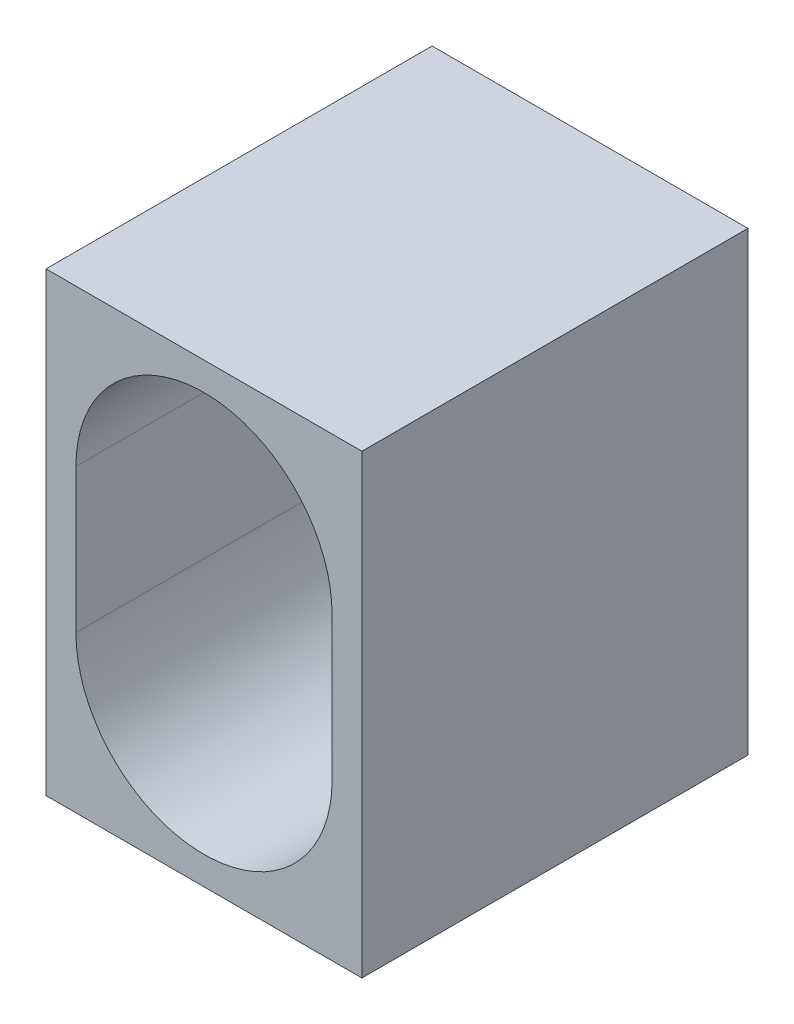
SolidWorks part; units mm, degrees
ref_plane "Front Plane" through (0, 0, 0) normal (0, 0, 1) x (1, 0, 0)
ref_plane "Top Plane" through (0, 0, 0) normal (0, 1, 0) x (1, 0, 0)
ref_plane "Right Plane" through (0, 0, 0) normal (1, 0, 0) x (0, 0, -1)
sketch "Sketch4" plane through (0, 0, 0) normal (0, 0, 1) x (1, 0, 0)
  line L1 (-30.2849, 20.5607) -> (14.7151, 20.5607)
  line L2 (-30.2849, 20.5607) -> (-30.2849, -44.4393)
  line L3 (-30.2849, -44.4393) -> (14.7151, -44.4393)
  line L4 (14.7151, 20.5607) -> (14.7151, -44.4393)
  dimension "D1" = 45
  dimension "D2" = 65
extrude "Boss-Extrude2" add sketch "Sketch4" along normal blind 55
sketch "Sketch5" plane through (0, 0, 55) normal (0, 0, 1) x (1, 0, 0)
  line L0 (-7.7849, -22.1893) -> (-7.7849, -1.6893) construction
  line L1 (-21.0349, -22.1893) -> (-21.0349, -1.6893) construction
  line L2 (5.4651, -22.1893) -> (5.4651, -1.6893) construction
  line L3 (-30.2849, -44.4393) -> (14.7151, -44.4393) construction
  line L4 (-30.2849, 20.5607) -> (-30.2849, -44.4393) construction
  line L5 (-26.0349, -22.1893) -> (-26.0349, -1.6893)
  line L6 (10.4651, -22.1893) -> (10.4651, -1.6893)
  arc A0 (-21.0349, -22.1893) -> (5.4651, -22.1893) centre (-7.7849, -22.1893) ccw construction
  arc A1 (5.4651, -1.6893) -> (-21.0349, -1.6893) centre (-7.7849, -1.6893) ccw construction
  arc A2 (10.4651, -1.6893) -> (-26.0349, -1.6893) centre (-7.7849, -1.6893) ccw
  arc A3 (-26.0349, -22.1893) -> (10.4651, -22.1893) centre (-7.7849, -22.1893) ccw
  point P2 (-7.7849, -11.9393)
  dimension "D3" = 5
  dimension "D1" = 32.5
  dimension "D2" = 22.5
extrude "Cut-Extrude1" cut sketch "Sketch5" against normal blind 52.5
